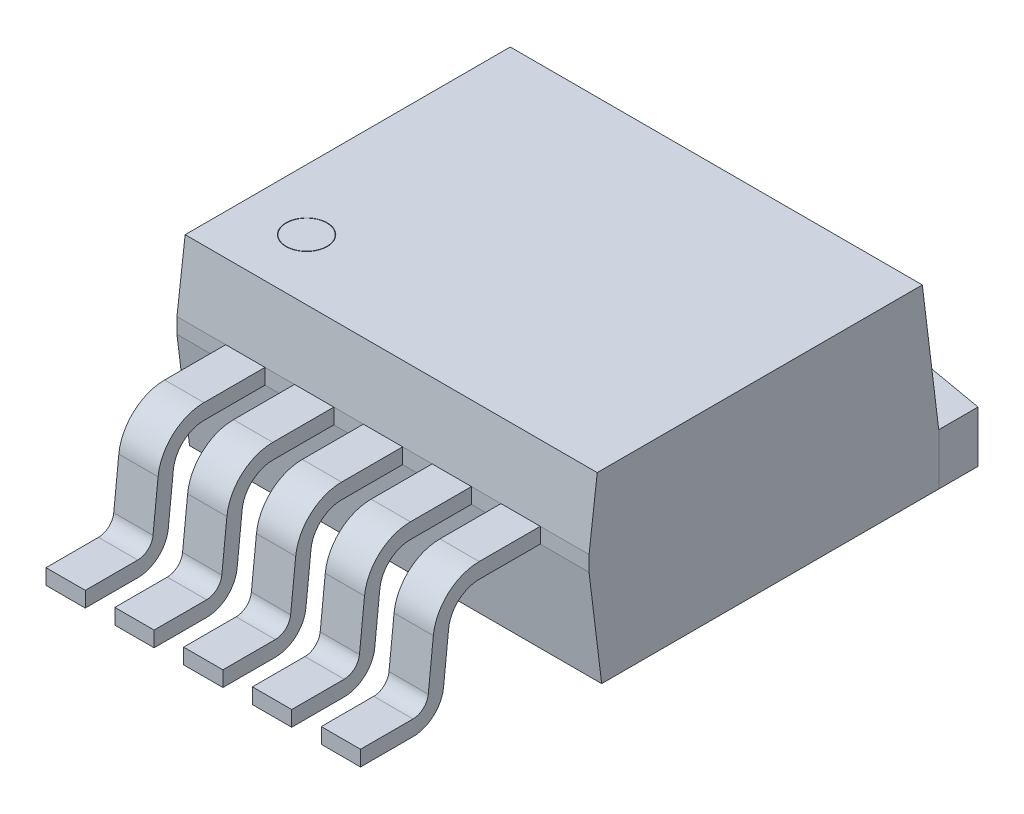
SolidWorks part; units mm, degrees
ref_plane "Спереди" through (0, 0, 0) normal (0, 0, 1) x (1, 0, 0)
ref_plane "Сверху" through (0, 0, 0) normal (0, 1, 0) x (1, 0, 0)
ref_plane "Справа" through (0, 0, 0) normal (1, 0, 0) x (0, 0, -1)
sketch "Эскиз2" plane through (0, 0, 0) normal (0, 1, 0) x (1, 0, 0)
  line L0 (-2.9, 0) -> (-2.9, 5.08) construction
  line L1 (-5.08, 0) -> (5.08, 0) construction
  line L2 (-5.08, 0) -> (-5.08, 6.35) construction
  line L3 (-5.08, 6.35) -> (5.08, 6.35) construction
  line L4 (5.08, 0) -> (5.08, 6.35) construction
  line L5 (-2.9, 5.08) -> (-5.08, 5.08) construction
  line L6 (2.9, 0) -> (2.9, 5.08) construction
  line L7 (0, 0) -> (0, 6.35) construction
  line L8 (-2.9, 5.08) -> (2.9, 5.08) construction
  line L9 (2.9, 5.08) -> (5.08, 5.08) construction
  line L10 (3.43, 6.35) -> (5.08, 6.0591)
  line L11 (-5.08, 5.08) -> (-2.9, 5.08)
  line L12 (-2.9, 5.08) -> (-2.9, 0)
  line L13 (5.08, 6.0591) -> (5.08, 5.08)
  line L14 (5.08, 5.08) -> (2.9, 5.08)
  line L15 (2.9, 5.08) -> (2.9, 0)
  line L16 (-2.9, 0) -> (2.9, 0)
  line L17 (3.43, 6.35) -> (-3.43, 6.35)
  line L18 (-3.43, 6.35) -> (-5.08, 6.0591)
  line L19 (-5.08, 6.0591) -> (-5.08, 5.08)
  point P4 (0, 0)
  point P5 (0, 5.08)
  point P13 (-2.9, 5.08)
  point P14 (2.9, 5.08)
  point P16 (0, 6.35)
  dimension "D1" = 10.16
  dimension "D2" = 5.08
  dimension "D3" = 1.27
  dimension "D4" = 5.8
  dimension "D5" = 6.86
  dimension "D6" = 10
  dimension "D7" = 10
extrude "Бобышка-Вытянуть1" add sketch "Эскиз2" along normal blind 1.27
sketch "Эскиз3" plane through (-5.08, 0, 0) normal (-1, 0, 0) x (0, 0, 1)
  line L0 (-5.08, 0.01) -> (-5.08, 1.27)
  line L2 (-6.0591, 1.27) -> (-5.08, 1.27) construction
  line L3 (-5.08, 1.27) -> (-4.6736, 4.58)
  line L4 (-4.6736, 4.58) -> (3.3574, 4.58)
  line L5 (3.3574, 4.58) -> (3.56, 2.93)
  line L6 (3.56, 2.93) -> (3.56, 2.55)
  line L7 (3.56, 2.55) -> (3.2481, 0.01)
  line L8 (3.2481, 0.01) -> (-5.08, 0.01)
  line L9 (-6.35, 1.27) -> (-6.35, 0) construction
  line L11 (-6.0591, 0) -> (-5.08, 0) construction
  dimension "D1" = 7
  dimension "D2" = 7
  dimension "D3" = 7
  dimension "D4" = 4.57
  dimension "D5" = 1.27
  dimension "D6" = 0.38
  dimension "D7" = 2.54
  dimension "D8" = 8.64
  dimension "D9" = 0.01
extrude "Бобышка-Вытянуть2" add sketch "Эскиз3" against normal offset from surface 0.01 and the other way blind 0.01 up to face at (5.08, 0.635, -5.5695) offset beyond the face yes
sketch "Эскиз4" plane through (0, 4.58, 0) normal (0, 1, 0) x (1, 0, 0)
  line L0 (-5.09, -3.3574) -> (-5.09, 4.6736) construction
  line L1 (-5.09, -3.3574) -> (5.09, -3.3574) construction
  circle A0 centre (-3.59, -1.8574) radius 0.5
  circle A1 centre (-3.59, -1.8574) radius 0.51
  dimension "D4" = 1
  dimension "D2" = 1.5
  dimension "D3" = 1.5
  dimension "D1" = 0.01
extrude "Вырез-Вытянуть1" cut sketch "Эскиз4" against normal blind 0.1
sketch "Эскиз5" plane through (0, 0, 0) normal (1, 0, 0) x (0, 0, -1)
  line L0 (-3.56, 2.93) -> (-3.56, 2.55)
  line L1 (-3.56, 2.55) -> (-5.0677, 2.55)
  line L2 (-5.8235, 1.8694) -> (-5.9485, 0.6806)
  line L3 (-6.7043, 0) -> (-8, 0)
  line L4 (6.35, 1.27) -> (6.35, 0) construction
  line L5 (-8, 0.38) -> (-8, 0)
  line L6 (-3.56, 2.93) -> (-5.0677, 2.93)
  line L7 (-6.2014, 1.9092) -> (-6.3264, 0.7203)
  line L8 (-6.7043, 0.38) -> (-8, 0.38)
  arc A0 (-5.8235, 1.8694) -> (-5.0677, 2.55) centre (-5.0677, 1.79) cw
  arc A1 (-5.9485, 0.6806) -> (-6.7043, 0) centre (-6.7043, 0.76) cw
  arc A2 (-6.2014, 1.9092) -> (-5.0677, 2.93) centre (-5.0677, 1.79) cw
  arc A3 (-6.3264, 0.7203) -> (-6.7043, 0.38) centre (-6.7043, 0.76) cw
  point P14 (-6.02, 0)
  dimension "D3" = 0.76
  dimension "D1" = 14.35
  dimension "D2" = 1.98
  dimension "D4" = 6
  dimension "D5" = 0.38
  dimension "D6" = 0.38
  dimension "D7" = 0.38
extrude "Бобышка-Вытянуть3" add sketch "Эскиз5" along normal blind 0.485 and the other way blind 0.485
pattern_linear "Линейный массив1" count 3 spacing 1.7 along (-1, 0, 0) count 3 spacing 1.7 along (1, 0, 0) of "Бобышка-Вытянуть3"
